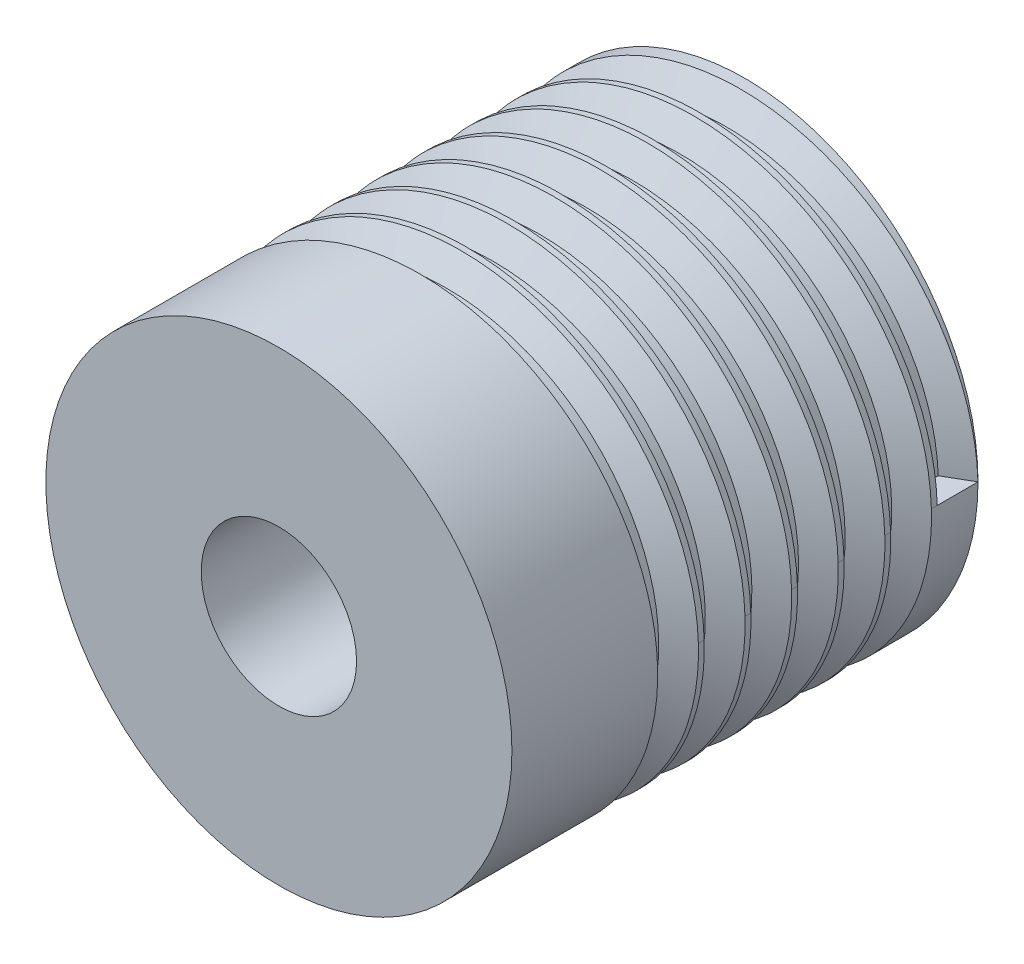
SolidWorks part; units mm, degrees
ref_plane "Front Plane" through (0, 0, 0) normal (0, 0, 1) x (1, 0, 0)
ref_plane "Top Plane" through (0, 0, 0) normal (0, 1, 0) x (1, 0, 0)
ref_plane "Right Plane" through (0, 0, 0) normal (1, 0, 0) x (0, 0, -1)
sketch "Sketch1" plane through (0, 0, 0) normal (0, 0, 1) x (1, 0, 0)
  circle A0 centre (0, 0) radius 7.5
extrude "Boss-Extrude1" add sketch "Sketch1" along normal blind 5 and the other way blind 10
sketch "Sketch2" plane through (0, 0, 5) normal (0, 0, 1) x (1, 0, 0)
  circle A0 centre (0, 0) radius 2.5
extrude "Cut-Extrude1" cut sketch "Sketch2" against normal through all
thread "Thread1" pitch 1.5 method cut profile "Thread Profile1" start angle 0, offset 0, length 10, pitch 1.5, diameter 15
ref_plane "Plane1" through (7.5, 0, -10) normal (0, -1, 0) x (1, 0, 0)
sketch "Thread Profile1" plane through (7.5, 0, -10) normal (0, -1, 0) x (1, 0, 0)
  line L0 (0, 0) -> (0, 1.5) construction
  line L11 (0, 0) -> (0, 1.3125)
  line L12 (0, 1.3125) -> (-0.8119, 0.8437)
  line L13 (-0.8119, 0.8437) -> (-0.8119, 0.4687)
  line L15 (-0.8119, 0.4687) -> (0, 0)
  line L17 (-0.8119, 0.6562) -> (0, 0.6562) construction
  point P2 (0, 0)
  dimension "Pitch" = 1.5
  dimension "Profile_Angle" = 60
  dimension "Profile_Land" = 0.375
  dimension "Profile_Height" = 0.8119
